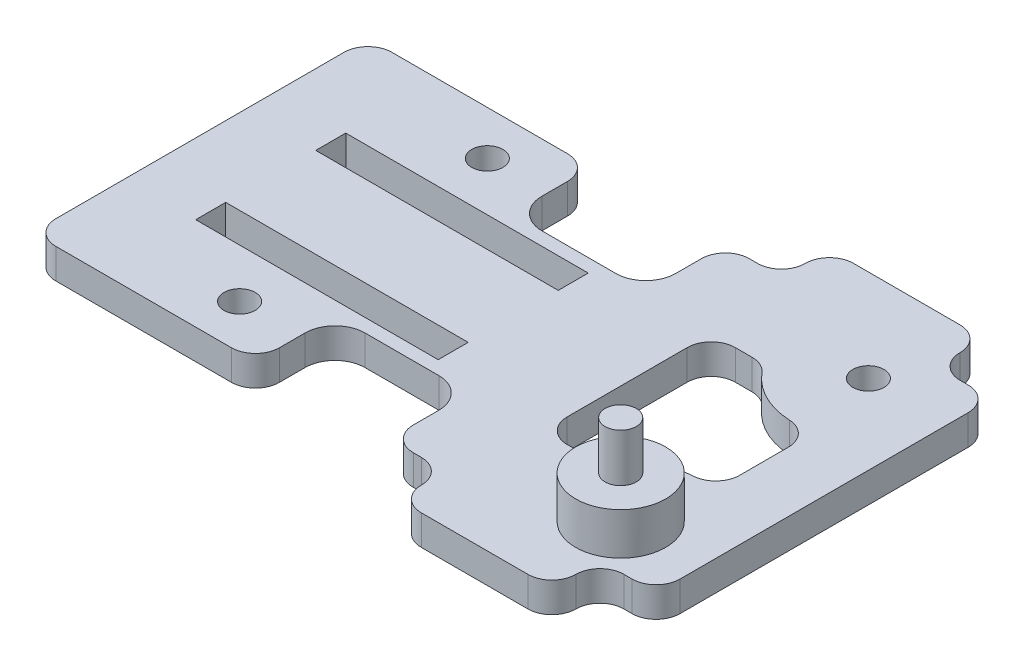
SolidWorks part; units mm, degrees
other "下垫片"
ref_plane "前视基准面" through (0, 0, 0) normal (0, 0, 1) x (1, 0, 0)
ref_plane "上视基准面" through (0, 0, 0) normal (0, 1, 0) x (1, 0, 0)
ref_plane "右视基准面" through (0, 0, 0) normal (1, 0, 0) x (0, 0, -1)
other "Configuration Table"
sketch "草图1" plane through (0, 0, 0) normal (0, 1, 0) x (1, 0, 0)
  line L0 (-89.3251, 0) -> (102.0425, 0) construction
  line L1 (0, 56.7239) -> (0, -62.578) construction
  line L2 (-47.2, -7.5) -> (-6.8, -7.5)
  line L3 (-47.2, 12.5) -> (-6.8, 12.5)
  line L4 (-47.2, 12.5) -> (-47.2, 7.5)
  line L5 (-47.2, 7.5) -> (-6.8, 7.5)
  line L6 (-6.8, 12.5) -> (-6.8, 7.5)
  line L7 (-47.2, 12.5) -> (-6.8, 7.5) construction
  line L8 (-47.2, 7.5) -> (-6.8, 12.5) construction
  line L9 (-6.8, -12.5) -> (-6.8, -7.5)
  line L10 (-47.2, -12.5) -> (-6.8, -12.5)
  line L11 (-47.2, -12.5) -> (-47.2, -7.5)
  line L14 (-21.75, -26.5375) -> (-21.75, -14.7375)
  line L15 (-21.75, -14.7375) -> (0.55, -14.7375)
  line L16 (0.55, -26.5375) -> (0.55, -14.7375)
  line L17 (-21.75, -26.5375) -> (0.55, -14.7375) construction
  line L18 (-21.75, -14.7375) -> (0.55, -26.5375) construction
  line L19 (-21.75, 14.7375) -> (0.55, 14.7375)
  line L20 (0.55, 26.5375) -> (0.55, 14.7375)
  line L22 (-21.75, 26.5375) -> (-21.75, 14.7375)
  line L23 (-21.75, 30.0095) -> (0.55, 30.0095)
  line L25 (-21.75, -26.5375) -> (-21.75, -30.0095)
  line L26 (-21.75, -30.0095) -> (0.55, -30.0095)
  line L27 (0.55, -26.5375) -> (0.55, -30.0095)
  line L28 (0.55, 26.5375) -> (0.55, 30.0095)
  line L30 (-21.75, 26.5375) -> (-21.75, 30.0095)
  circle A0 centre (-31.75, 20.6375) radius 2.6
  circle A4 centre (31.75, 20.6375) radius 2.6
  circle A5 centre (31.75, -20.6375) radius 2.6
  circle A6 centre (-31.75, -20.6375) radius 2.6
  point P13 (-27, 10)
  point P22 (-10.6, -20.6375)
  point P35 (-27, 10)
  dimension "D5" = 5.2
  dimension "D11" = 5.2
  dimension "D1" = 40.4
  dimension "D2" = 31.75
  dimension "D3" = 5
  dimension "D4" = 20.6375
  dimension "D6" = 10
  dimension "D7" = 22.3
  dimension "D8" = 11.8
  dimension "D9" = 0
  dimension "D10" = 31.2
  dimension "D12" = 5
  dimension "D13" = 40.4
  dimension "D14" = 27
  dimension "D15" = 10
  dimension "D16" = 2.2375
sketch "草图3" plane through (0, 0, 0) normal (0, 1, 0) x (1, 0, 0)
  line L0 (-40, 28) -> (-59, 28)
  line L1 (-40, -28) -> (9.9, -28)
  line L3 (-40, 28) -> (9.9, 28)
  line L5 (-40, -28) -> (40, 28) construction
  line L6 (-40, 28) -> (40, -28) construction
  line L7 (-59, 28) -> (-59, -28)
  line L8 (-59, -28) -> (-40, -28)
  line L10 (45, 28) -> (45, -28)
  line L15 (-45.7746, 0) -> (58.2399, 0) construction
  line L19 (9.9, 28) -> (9.9, 36)
  line L20 (9.9, 36) -> (35.65, 36)
  line L21 (35.65, 36) -> (35.65, 28)
  line L22 (35.65, 28) -> (45, 28)
  line L23 (35.65, -28) -> (45, -28)
  line L24 (35.65, -36) -> (35.65, -28)
  line L25 (9.9, -36) -> (35.65, -36)
  line L26 (9.9, -28) -> (9.9, -36)
  point P0 (0, 0)
  dimension "D1" = 56
  dimension "D2" = 80
  dimension "D3" = 19
  dimension "D4" = 5
  dimension "D5" = 9.35
  dimension "D6" = 8
  dimension "D7" = 25.75
extrude "凸台-拉伸1" add sketch "草图3" along normal blind 5
extrude "切除-拉伸1" cut sketch "草图1" along normal up to surface (5 mm away) up to face at (12.85, 5, 0)
sketch "草图5" plane through (0, 5, 0) normal (0, 1, 0) x (1, 0, 0)
  circle A0 centre (31.75, -20.6375) radius 7.5
  dimension "D1" = 15
extrude "凸台-拉伸2" add sketch "草图5" along normal blind 7
sketch "草图6" plane through (0, 12, 0) normal (0, 1, 0) x (1, 0, 0)
  circle A0 centre (31.75, -20.6375) radius 2.6
  dimension "D1" = 5.2
extrude "凸台-拉伸3" add sketch "草图6" along normal blind 8
fillet "圆角1" radius 5 4 edges at (0.55, 2.5, 14.7375) (-21.75, 2.5, 14.7375) (0.55, 2.5, -14.7375) (-21.75, 2.5, -14.7375)
fillet "圆角2" radius 4 16 edges at (0.55, 2.5, 28) (-21.75, 2.5, 28) (0.55, 2.5, -28) (-21.75, 2.5, -28) (-59, 2.5, 28) (-59, 2.5, -28) (9.9, 2.5, 28) (9.9, 2.5, 36) (35.65, 2.5, 36) (35.65, 2.5, 28) (45, 2.5, 28) (45, 2.5, -28) (35.65, 2.5, -28) (35.65, 2.5, -36) (9.9, 2.5, -36) (9.9, 2.5, -28)
sketch "草图7" plane through (0, 0, 0) normal (0, -1, 0) x (1, 0, 0)
  line L0 (-31.75, 20.6375) -> (31.75, 20.6375) construction
  line L1 (0, 27.9483) -> (0, -23.2551) construction
sketch "草图14" plane through (0, 5, 0) normal (0, 1, 0) x (1, 0, 0)
  line L0 (-11.6114, 0) -> (10.899, 0) construction
  line L1 (21.04, 14) -> (12.2, 14)
  line L2 (12.2, 14) -> (12.2, -14)
  line L3 (45, -24) -> (45, 24) construction
  line L4 (35, 8.4639) -> (35, -8.4639)
  line L5 (21.04, -14) -> (12.2, -14)
  arc A0 (35, 8.4639) -> (21.04, 14) centre (31.75, 20.6375) cw
  arc A1 (35, -8.4639) -> (21.04, -14) centre (31.75, -20.6375) ccw
  point P5 (35, 0)
  point P7 (21.04, 14)
  point P8 (35, 8.4639)
  point P18 (12.2, 0)
  dimension "D1" = 12.6
  dimension "D2" = 14
  dimension "D3" = 12.2
  dimension "D4" = 10
extrude "切除-拉伸6" cut sketch "草图14" against normal through all
fillet "圆角5" radius 4 6 edges at (35, 2.5, 8.4639) (21.04, 2.5, 14) (12.2, 2.5, 14) (21.04, 2.5, -14) (35, 2.5, -8.4639) (12.2, 2.5, -14)
